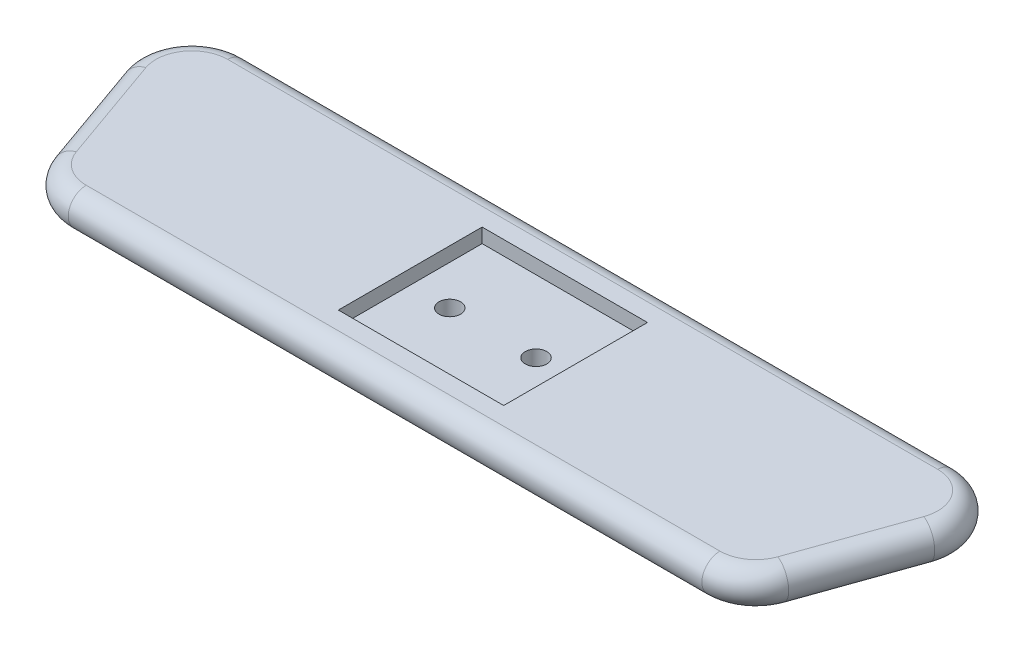
SolidWorks part; units mm, degrees
ref_plane "Front Plane" through (0, 0, 0) normal (0, 0, 1) x (1, 0, 0)
ref_plane "Top Plane" through (0, 0, 0) normal (0, 1, 0) x (1, 0, 0)
ref_plane "Right Plane" through (0, 0, 0) normal (1, 0, 0) x (0, 0, -1)
sketch "Sketch1" plane through (0, 0, 0) normal (0, 1, 0) x (1, 0, 0)
  line L0 (-112.9151, 9.9929) -> (-102.2916, -20.0071)
  line L1 (-88.1519, -30) -> (88.1519, -30)
  line L3 (-98.7755, 30) -> (98.7755, 30)
  line L7 (0, -33) -> (0, 33) construction
  line L8 (112.9151, 9.9929) -> (102.2916, -20.0071)
  arc A0 (98.7755, 30) -> (112.9151, 9.9929) centre (98.7755, 15) cw
  arc A1 (102.2916, -20.0071) -> (88.1519, -30) centre (88.1519, -15) cw
  arc A2 (-102.2916, -20.0071) -> (-88.1519, -30) centre (-88.1519, -15) ccw
  arc A3 (-112.9151, 9.9929) -> (-98.7755, 30) centre (-98.7755, 15) cw
  point P0 (0, 0)
  point P10 (120, 30)
  point P13 (98.7529, -30)
  point P16 (-98.7529, -30)
  point P19 (-120, 30)
  dimension "D2" = 15
  dimension "D1" = 240
  dimension "D3" = 70.5
extrude "Boss-Extrude2" add sketch "Sketch1" along normal blind 10 contours L3 A0 L8 A1 L1 A2 L0 A3
fillet "Fillet2" 16 edges at (-111.0251, 10, -23.6572) (-107.6033, 10, 5.0071) (-96.8091, 10, 27.2496) (0, 10, 30) (96.8091, 10, 27.2496) (107.6033, 10, 5.0071) (111.0251, 10, -23.6572) (0, 10, -30) (-111.0251, 0, -23.6572) (-107.6033, 0, 5.0071) (-96.8091, 0, 27.2496) (0, 0, 30) (96.8091, 0, 27.2496) (107.6033, 0, 5.0071) (111.0251, 0, -23.6572) (0, 0, -30) type full round first side face at (0, 10, 2.1499) second side face at (0, 0, 2.1499) middle face at (0, 5, -30) middle face at (-108.4352, 5, -21.8268) middle face at (-96.0154, 5, 26.1266) middle face at (-107.6033, 5, 5.0071) middle face at (108.4352, 5, -21.8268) middle face at (107.6033, 5, 5.0071) middle face at (96.0154, 5, 26.1266) middle face at (0, 5, 30)
sketch "Sketch3" plane through (0, 10, 0) normal (0, 1, 0) x (1, 0, 0)
  line L1 (-23, -20) -> (23, -20)
  line L2 (-23, -20) -> (-23, 20)
  line L3 (-23, 20) -> (23, 20)
  line L4 (23, -20) -> (23, 20)
  line L5 (-23, -20) -> (23, 20) construction
  line L6 (-23, 20) -> (23, -20) construction
  point P0 (0, 0)
  dimension "D1" = 46
  dimension "D2" = 40
extrude "Cut-Extrude1" cut sketch "Sketch3" against normal blind 4
sketch "Sketch4" plane through (0, 6, 0) normal (0, 1, 0) x (1, 0, 0)
  line L0 (-5.5001, 0) -> (5.5001, 0) construction
  line L1 (0, -5.5001) -> (0, 5.5001) construction
  circle A0 centre (12, 0) radius 3
  circle A1 centre (-12, 0) radius 3
  dimension "D1" = 12
extrude "Cut-Extrude2" cut sketch "Sketch4" against normal blind 6
sketch "Sketch5" plane through (0, 10, 0) normal (0, 1, 0) x (1, 0, 0)
  line L0 (-5.5001, 0) -> (5.5001, 0) construction
  line L1 (0, -5.5001) -> (0, 5.5001) construction
  circle A0 centre (-70, 8) radius 2
  circle A1 centre (-70, -8) radius 2
  circle A2 centre (70, -8) radius 2
  circle A3 centre (70, 8) radius 2
  dimension "D1" = 8
  dimension "D2" = 70
extrude "Cut-Extrude3" cut sketch "Sketch5" against normal blind 8 from offset 2 offset against normal yes
